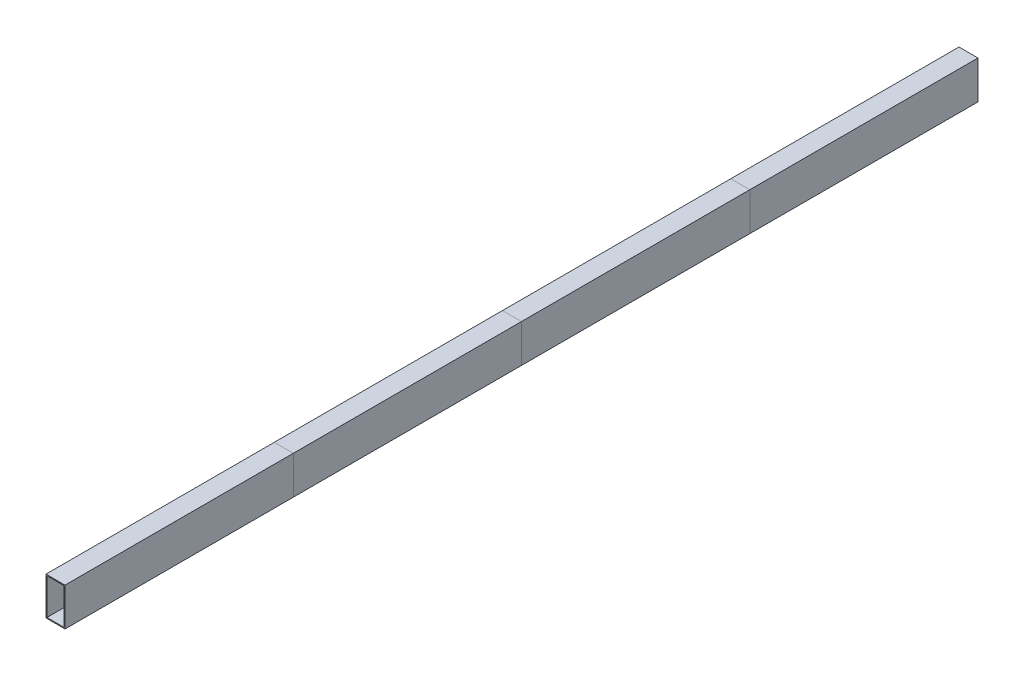
SolidWorks part; units mm, degrees
ref_plane "Спереди" through (0, 0, 0) normal (0, 0, 1) x (1, 0, 0)
ref_plane "Сверху" through (0, 0, 0) normal (0, 1, 0) x (1, 0, 0)
ref_plane "Справа" through (0, 0, 0) normal (1, 0, 0) x (0, 0, -1)
sketch "Эскиз1" plane through (0, 0, 0) normal (0, 0, 1) x (1, 0, 0)
  line L1 (-50, -100) -> (50, -100)
  line L2 (-50, -100) -> (-50, 100)
  line L3 (-50, 100) -> (50, 100)
  line L4 (50, -100) -> (50, 100)
  line L5 (-50, -100) -> (50, 100) construction
  line L6 (-50, 100) -> (50, -100) construction
  line L7 (-45, -95) -> (45, -95)
  line L8 (-45, -95) -> (-45, 95)
  line L9 (-45, 95) -> (45, 95)
  line L10 (45, -95) -> (45, 95)
  line L11 (-45, -95) -> (45, 95) construction
  line L12 (-45, 95) -> (45, -95) construction
  point P0 (0, 0)
  point P6 (0, 0)
  dimension "D1" = 100
  dimension "D2" = 200
  dimension "D3" = 190
  dimension "D4" = 90
extrude "Бобышка-Вытянуть1" add sketch "Эскиз1" along normal blind 1200
extrude "Бобышка-Вытянуть2" add sketch "Эскиз1<2>" along normal blind 1200 from surface separate body starting at face at (0, 0, 1200)
sketch "Эскиз1<2>" plane through (0, 0, 0) normal (0, 0, 1) x (1, 0, 0) same geometry as "Эскиз1"
extrude "Бобышка-Вытянуть3" add sketch "Эскиз1<3>" along normal blind 1200 from surface separate body starting at face at (0, 0, 2400)
sketch "Эскиз1<3>" plane through (0, 0, 0) normal (0, 0, 1) x (1, 0, 0) same geometry as "Эскиз1"
extrude "Бобышка-Вытянуть4" add sketch "Эскиз1<4>" along normal blind 1200 from surface separate body starting at face at (0, 0, 3600)
sketch "Эскиз1<4>" plane through (0, 0, 0) normal (0, 0, 1) x (1, 0, 0) same geometry as "Эскиз1"
ref_point "Точка1"
ref_point "Точка2"
